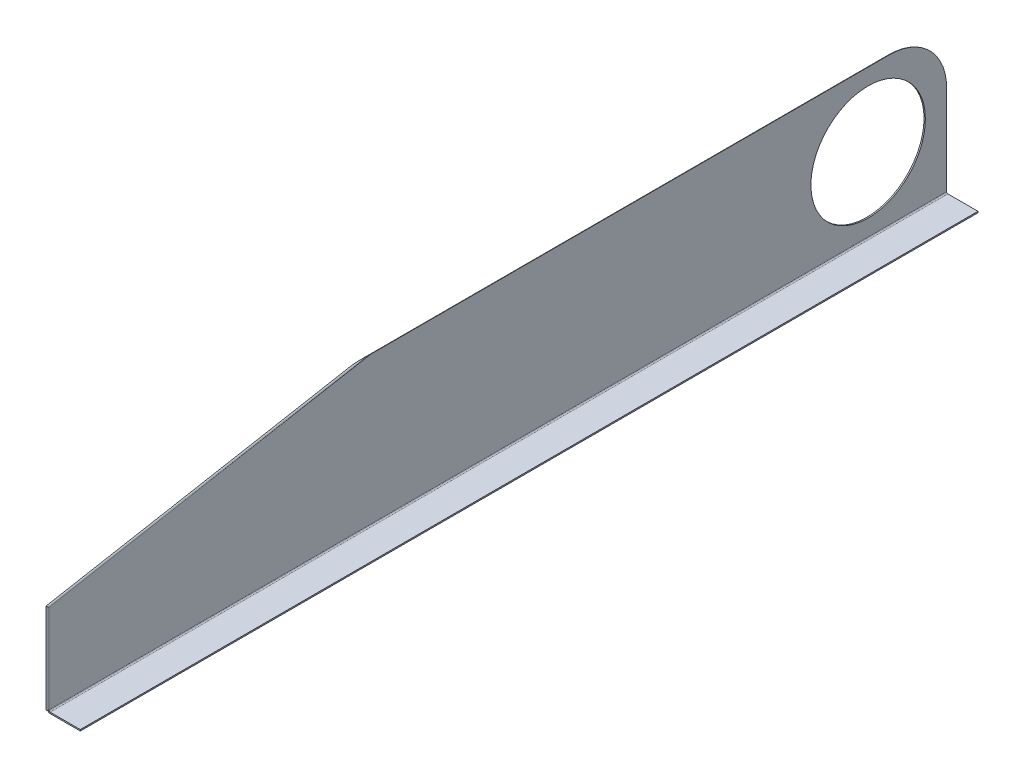
SolidWorks part; units mm, degrees
note: The reader was unsure of these and kept them because the rebuilt part matched: flange length of "Edge-Flange1".
ref_plane "Front Plane" through (0, 0, 0) normal (0, 0, 1) x (1, 0, 0)
ref_plane "Top Plane" through (0, 0, 0) normal (0, 1, 0) x (1, 0, 0)
ref_plane "Right Plane" through (0, 0, 0) normal (1, 0, 0) x (0, 0, -1)
sketch "Sketch1" plane through (0, 0, 0) normal (1, 0, 0) x (0, 0, -1)
  line L0 (-275, 10.1014) -> (-82.9653, 45)
  line L1 (275, -45) -> (-275, -45)
  line L2 (275, -45) -> (275, 45)
  line L3 (275, 45) -> (-82.9653, 45)
  line L4 (-275, -45) -> (-275, 10.1014)
  point P0 (0, 0)
  point P1 (0, 0)
  dimension "D1" = 550
  dimension "D2" = 90
  dimension "D3" = 195.18
  dimension "D4" = 10.3
base flange "Base-Flange1" sketch "Sketch1" thickness 0.8 reverse thickness direction no parameters "D1"=0.8
sketch "Sketch6" plane through (0, 0, 0) normal (1, 0, 0) x (0, 0, -1)
  line L2 (0.8621, 0) -> (-0.8621, 0) construction
  circle A0 centre (227, 0) radius 35
  dimension "D2" = 70
extrude "Cut-Extrude1" cut sketch "Sketch6" against normal blind 10
sketch "Sketch7" plane through (0, 0, 0) normal (1, 0, 0) x (0, 0, -1)
  line L0 (275, 45) -> (240, 45)
  line L6 (275, 45) -> (-82.9653, 45) construction
  line L8 (275, 45) -> (275, 10)
  line L9 (275, -45) -> (275, 45) construction
  arc A0 (275, 10) -> (240, 45) centre (240, 10) ccw
  dimension "D1" = 35
  dimension "D2" = 35
extrude "Cut-Extrude2" cut sketch "Sketch7" against normal blind 10
fillet "Fillet1" radius 1 1 edges at (0, 27.5507, 178.9827)
fillet "Fillet2" radius 1 3 edges at (-0.8, -17.5, -275) (-0.8, 34.7487, -264.7487) (-0.8, 45, -78.5173)
fillet "Fillet5" radius 1 1 edges at (0, -17.9472, 275)
edge flange "Edge-Flange1" sketch "Sketch10" flange angle 90 flange length 20 flange position bend outside bend radius 0.8 thickness 0.8 parameters "D6"=10
sketch "Sketch10" plane through (0, -45, 0) normal (0, -1, 0) x (0, 0, -1)
  line L2 (-274.0202, 0) -> (-274.0202, 19.2)
  line L3 (-274.0202, 19.2) -> (275, 19.2)
  line L4 (275, 19.2) -> (275, 0)
  line L9 (-274.0202, 0) -> (275, 0) construction
  line L10 (-274.0202, 0) -> (275, 0)
bend "EdgeBend1" bend radius 0.8 bend angle 90 parameters "D5"=1
sketch "Bend-Lines1" [suppressed] plane through (0, 0, 0) normal (0, 1, 0) x (1, 0, 0)
sketch "Bounding-Box1" [suppressed] plane through (0, 0, 0) normal (0, 1, 0) x (1, 0, 0)
sheet metal parameters "Sheet-Metal1" thickness 0.8 parameters "D1"=0.8
flat pattern "Flat-Pattern1" [suppressed]
sketch "Bend-Lines2" plane through (0, 0, 0) normal (0, 1, 0) x (1, 0, 0)
sketch3d "Bounding-Box2" [suppressed]
  line L0 (275, -45, 0) -> (-275, -45, 0) construction
  line L1 (275, 45, 0) -> (-275, 45, 0) construction
  line L2 (275, -45, 0) -> (275, 45, 0) construction
  line L3 (-275, -45, 0) -> (-275, 45, 0) construction
sheet metal parameters "Sheet-Metal2" thickness 0.8 parameters "D1"=0.8
flat pattern "Flat-Pattern1"
sketch "Bend-Lines2" plane through (0, 0, 0) normal (0, 1, 0) x (1, 0, 0)
sketch3d "Bounding-Box2" [suppressed]
  line L0 (-275, -45, 0) -> (275, -45, 0) construction
  line L1 (-275, 45, 0) -> (275, 45, 0) construction
  line L2 (-275, -45, 0) -> (-275, 45, 0) construction
  line L3 (275, -45, 0) -> (275, 45, 0) construction
sheet metal parameters "Sheet-Metal3" thickness 0.8 parameters "D1"=0.8
flat pattern "Flat-Pattern1"
sketch "Bend-Lines2" plane through (0, 0, 0) normal (0, 1, 0) x (1, 0, 0)
sketch3d "Bounding-Box2" [suppressed]
  line L0 (-274.0202, 45, 0) -> (275, 45, 0) construction
  line L1 (-274.0202, -45, 0) -> (275, -45, 0) construction
  line L2 (-274.0202, 45, 0) -> (-274.0202, -45, 0) construction
  line L3 (275, 45, 0) -> (275, -45, 0) construction
sheet metal parameters "Sheet-Metal4" thickness 0.8 parameters "D1"=0.8
flat pattern "Flat-Pattern1"
sketch "Bend-Lines2" plane through (0, 0, 0) normal (1, 0, 0) x (0, 0, -1)
  line L0 (-274.0202, -45.9111) -> (275, -45.9111) construction
  line L1 (-274.0202, -45.9111) -> (275, -45.9111) construction
sketch3d "Bounding-Box2" [suppressed]
  line L0 (-274.0202, 45, 0) -> (275, 45, 0) construction
  line L1 (-274.0202, -65.2221, 0) -> (275, -65.2221, 0) construction
  line L2 (-274.0202, 45, 0) -> (-274.0202, -65.2221, 0) construction
  line L3 (275, 45, 0) -> (275, -65.2221, 0) construction
bend of the flat pattern "Flatten-<EdgeBend1>1"
